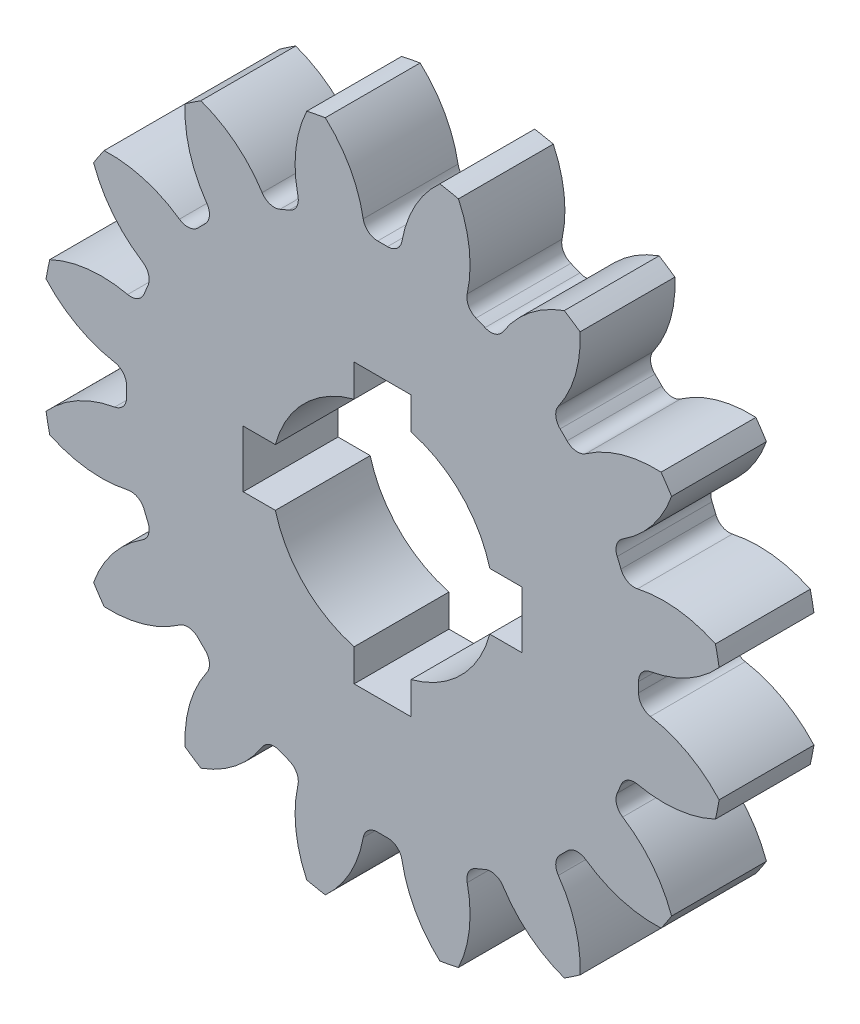
SolidWorks part; units mm, degrees
ref_plane "Front Plane" through (0, 0, 0) normal (0, 0, 1) x (1, 0, 0)
ref_plane "Top Plane" through (0, 0, 0) normal (0, 1, 0) x (1, 0, 0)
ref_plane "Right Plane" through (0, 0, 0) normal (1, 0, 0) x (0, 0, -1)
sketch "Sketch1" plane through (0, 0, 0) normal (0, 0, 1) x (1, 0, 0)
  line L4 (-0.9406, 13.4672) -> (0, 0) construction
  line L5 (0, 0) -> (0, 18) construction
  line L6 (0, 0) -> (3.5116, 17.6541) construction
  line L7 (-1.6208, 15.9177) -> (0.7278, 17.0537) construction
  line L8 (-1.6208, 15.9177) -> (0.394, 16.1228) construction
  line L11 (1.6208, 15.9177) -> (-1.6208, 15.9177) construction
  circle A0 centre (0, 0) radius 13.5
  circle A1 centre (0, 0) radius 16 construction
  circle A2 centre (0, 0) radius 18
  arc A3 (-3.0199, 17.7449) -> (-0.9406, 13.4672) centre (-7.293, 13.0235) cw
  arc A4 (3.0199, 17.7449) -> (0.9406, 13.4672) centre (7.293, 13.0235) ccw
  point P5 (-16, 0)
  point P6 (-18, 0)
  point P7 (-13.5, 0)
  point P12 (-1.6208, 15.9177)
  point P22 (1.6208, 15.9177)
  dimension "D5" = 32
  dimension "D1" = 2.5
  dimension "D2" = 2
  dimension "D3" = 20
  dimension "D4" = 3.2416
  dimension "D6" = 11.25
  dimension "D7" = 0.5
extrude "Boss-Extrude1" add sketch "Sketch1" against normal blind 5 contours A2
extrude "Cut-Extrude1" cut sketch "Sketch1<4>" against normal blind 10 contours A4 A2 A3 A0 region at (0, 16.173, 0)
sketch "Sketch1<4>" plane through (0, 0, 0) normal (0, 0, 1) x (1, 0, 0) same geometry as "Sketch1"
fillet "Fillet2" radius 0.76 2 edges at (0.9406, 13.4672, -2.5) (-0.9406, 13.4672, -2.5)
ref_axis "Axis1" through (0, 0, 0) along (0, 0, 1)
pattern_circular "CirPattern2" count 16 over 360 about axis through (0, 0, 0) along (0, 0, 1) of "Cut-Extrude1", "Fillet2"
sketch "Sketch2" plane through (0, 0, 0) normal (0, 0, 1) x (1, 0, 0)
  line L0 (-1.5, 5.6528) -> (-1.5, 7.3485)
  line L1 (-1.5, 4.3485) -> (1.5, 4.3485) construction
  line L2 (-1.5, 4.3485) -> (-1.5, 7.3485) construction
  line L3 (-1.5, 7.3485) -> (1.5, 7.3485) construction
  line L4 (1.5, 4.3485) -> (1.5, 7.3485) construction
  line L5 (-1.5, 4.3485) -> (1.5, 7.3485) construction
  line L6 (-1.5, 7.3485) -> (1.5, 4.3485) construction
  line L7 (4.3485, -1.5) -> (7.3485, -1.5) construction
  line L8 (4.3485, -1.5) -> (4.3485, 1.5) construction
  line L9 (4.3485, 1.5) -> (7.3485, 1.5) construction
  line L10 (7.3485, -1.5) -> (7.3485, 1.5) construction
  line L11 (4.3485, -1.5) -> (7.3485, 1.5) construction
  line L12 (4.3485, 1.5) -> (7.3485, -1.5) construction
  line L13 (-1.5, -7.3485) -> (1.5, -7.3485) construction
  line L14 (-1.5, -7.3485) -> (-1.5, -4.3485) construction
  line L15 (-1.5, -4.3485) -> (1.5, -4.3485) construction
  line L16 (1.5, -7.3485) -> (1.5, -4.3485) construction
  line L17 (-1.5, -7.3485) -> (1.5, -4.3485) construction
  line L18 (-1.5, -4.3485) -> (1.5, -7.3485) construction
  line L19 (-7.3485, -1.5) -> (-4.3485, -1.5) construction
  line L20 (-7.3485, -1.5) -> (-7.3485, 1.5) construction
  line L21 (-7.3485, 1.5) -> (-4.3485, 1.5) construction
  line L22 (-4.3485, -1.5) -> (-4.3485, 1.5) construction
  line L23 (-7.3485, -1.5) -> (-4.3485, 1.5) construction
  line L24 (-7.3485, 1.5) -> (-4.3485, -1.5) construction
  line L25 (-1.5, 7.3485) -> (1.5, 7.3485)
  line L26 (1.5, 7.3485) -> (1.5, 5.6528)
  line L27 (5.6528, 1.5) -> (7.3485, 1.5)
  line L28 (7.3485, 1.5) -> (7.3485, -1.5)
  line L29 (7.3485, -1.5) -> (5.6528, -1.5)
  line L30 (1.5, -7.3485) -> (1.5, -5.6528)
  line L31 (1.5, -7.3485) -> (-1.5, -7.3485)
  line L32 (-1.5, -7.3485) -> (-1.5, -5.6528)
  line L33 (-5.6528, -1.5) -> (-7.3485, -1.5)
  line L34 (-7.3485, -1.5) -> (-7.3485, 1.5)
  line L35 (-7.3485, 1.5) -> (-5.6528, 1.5)
  circle A0 centre (0, 0) radius 7.5 construction
  arc A1 (-1.5, 5.6528) -> (-5.6528, 1.5) centre (0, 0) ccw
  arc A2 (5.6528, 1.5) -> (1.5, 5.6528) centre (0, 0) ccw
  arc A3 (1.5, -5.6528) -> (5.6528, -1.5) centre (0, 0) ccw
  arc A4 (-5.6528, -1.5) -> (-1.5, -5.6528) centre (0, 0) ccw
  point P3 (0, 5.8485)
  point P8 (5.8485, 0)
  point P13 (0, -5.8485)
  point P18 (-5.8485, 0)
  dimension "D1" = 15
  dimension "D2" = 3
extrude "Cut-Extrude2" cut sketch "Sketch2" against normal up to surface (5 mm away) up to face at (0, 0, -5)
equation "\"backlash\"= 0.1mm"
equation "\"module\"= 2mm"
equation "\"pressureAngle\"= 20deg"
equation "\"width\"= 10mm"
equation "\"D1@Sketch1\"= 1.25 * \"module\""
equation "\"D2@Sketch1\"=\"module\""
equation "\"D5@Sketch1\"=\"module\"*\"numberOfTeeth\""
equation "\"D1@Boss-Extrude1\"=\"width\"-5"
equation "\"D3@Sketch1\"=\"pressureAngle\""
equation "\"D1@Cut-Extrude1\"=\"width\""
equation "\"D1@CirPattern2\"=\"numberOfTeeth\""
equation "\"D1@Fillet2\"=0.38*\"module\""
equation "\"D4@Sketch1\"=pi*\"module\"/2+\"backlash\""
equation "\"numberOfTeeth\"= 16"
equation "\"D6@Sketch1\"=180/\"numberOfTeeth\""
equation "\"toothTipProfile\"= 1mm"
equation "\"D7@Sketch1\"=\"toothTipProfile\"/2"
equation "\"lengthOverallRack\"= pi * \"module\" * \"numberOfTeethRack\""
equation "\"numberOfTeethRack\"= 20"
